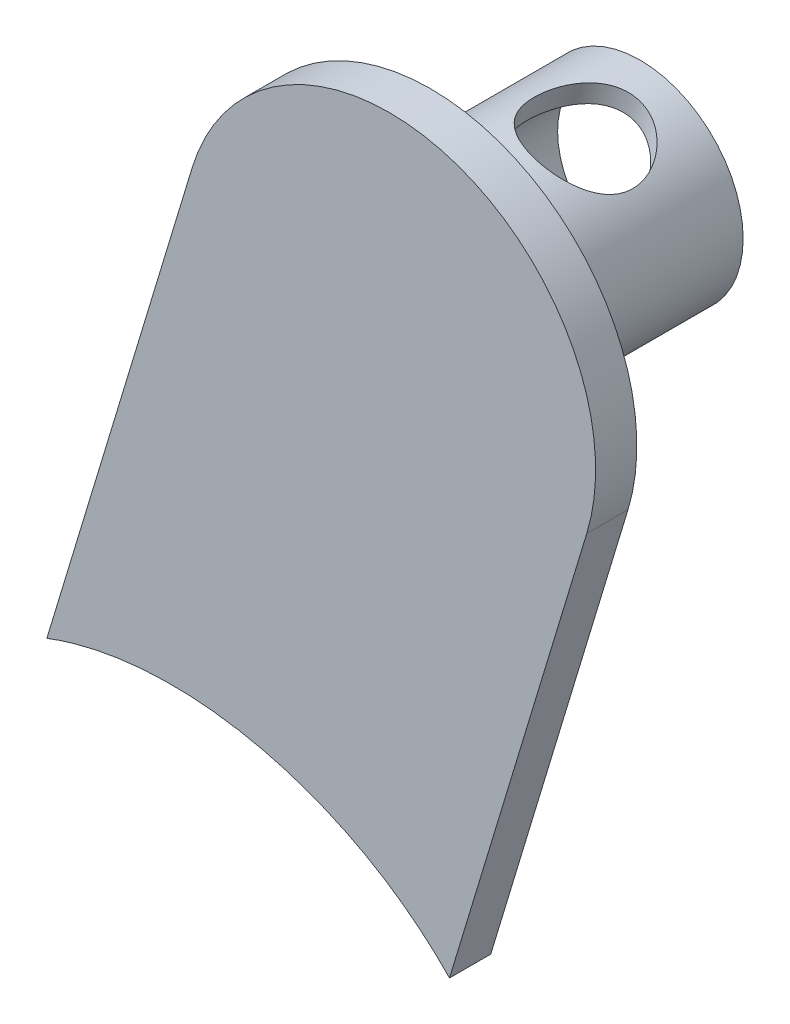
SolidWorks part; units mm, degrees
material "1.4105 (X6CrMoS17)"
ref_plane "Płaszczyzna XY" through (0, 0, 0) normal (0, 0, 1) x (1, 0, 0)
ref_plane "Płaszczyzna XZ" through (0, 0, 0) normal (0, 1, 0) x (1, 0, 0)
ref_plane "Płaszczyzna YZ" through (0, 0, 0) normal (1, 0, 0) x (0, 0, -1)
ref_plane "Płaszczyzna1" through (0, 0, 617.9993) normal (0, 0, -1) x (-1, 0, 0)
sketch "Szkic7" plane through (0, 0, 617.9993) normal (0, 0, -1) x (-1, 0, 0)
  line L2 (-1236.2588, -248.2211) -> (-1242.9178, -226.2171)
  line L3 (-1216.7266, -243.7155) -> (-1223.7752, -220.424)
  arc A1 (-1242.9178, -226.2171) -> (-1223.7752, -220.424) centre (-1233.3465, -223.3205) cw
  spline S0 degree 3 poles (-1209.3452, -251.377) (-1215.7161, -227.2024) (-1246.0221, -235.1891) (-1239.6513, -259.3637) (-1233.2804, -283.5383) (-1202.9744, -275.5516) (-1209.3452, -251.377) (-1215.7161, -227.2024) (-1246.0221, -235.1891) knots -0.5 0 0 0 0.5 0.5 0.5 1 1 1 1.5 1.5 1.5 weights 1 0.333333 0.333333 1 0.333333 0.333333 1 0.333333 0.333333 only from (-1209.3452, -251.377) to (-1209.3452, -251.377)
  spline S1 degree 3 poles (-1216.7266, -243.7155) (-1223.4433, -241.1477) (-1231.1512, -242.8799) (-1236.2588, -248.2211) knots 0.154039 0.154039 0.154039 0.154039 0.334986 0.334986 0.334986 0.334986 weights 0.573668 0.481061 0.475765 0.557781
  dimension "D4" = 22.004
  dimension "D5" = 20
  dimension "D6" = 24.3347
  dimension "D7" = 1233.3465
extrude "Dodanie-wyciągnięcie1" add sketch "Szkic7" along normal blind 2
ref_plane "Płaszczyzna2" through (0, 0, 615.9993) normal (0, 0, -1) x (-1, 0, 0)
sketch "Szkic8" plane through (0, 0, 615.9993) normal (0, 0, -1) x (-1, 0, 0)
  line L0 (-1242.9178, -226.2171) -> (-1236.2588, -248.2211) construction
  circle A0 centre (-1233.5042, -222.0341) radius 4
  dimension "D1" = 10.2217
  dimension "D2" = 8
  dimension "D3" = 1233.5042
extrude "Extrude-Thin1" add sketch "Szkic8" along normal blind 10 thin contours A0 thin type one direction wall 1
ref_plane "Plane1" through (43.3821, 143.3521, 0) normal (0.2897, 0.9571, 0) x (0.9571, -0.2897, 0)
ref_axis "Axis1" through (1233.5042, -222.0341, 605.9993) along (0, 0, 1)
sketch "Sketch1" plane through (43.3821, 143.3521, 0) normal (0.2897, 0.9571, 0) x (0.9571, -0.2897, 0)
  line L0 (1249.9388, -605.9993) -> (1239.9388, -605.9993) construction
  line L1 (1244.9388, -605.9993) -> (1244.9388, -615.9993) construction
  circle A0 centre (1244.9388, -609.9993) radius 2.5
  dimension "D1" = 5
  dimension "D2" = 4
extrude "Cut-Extrude1" cut sketch "Sketch1" against normal blind 20 contours A0
